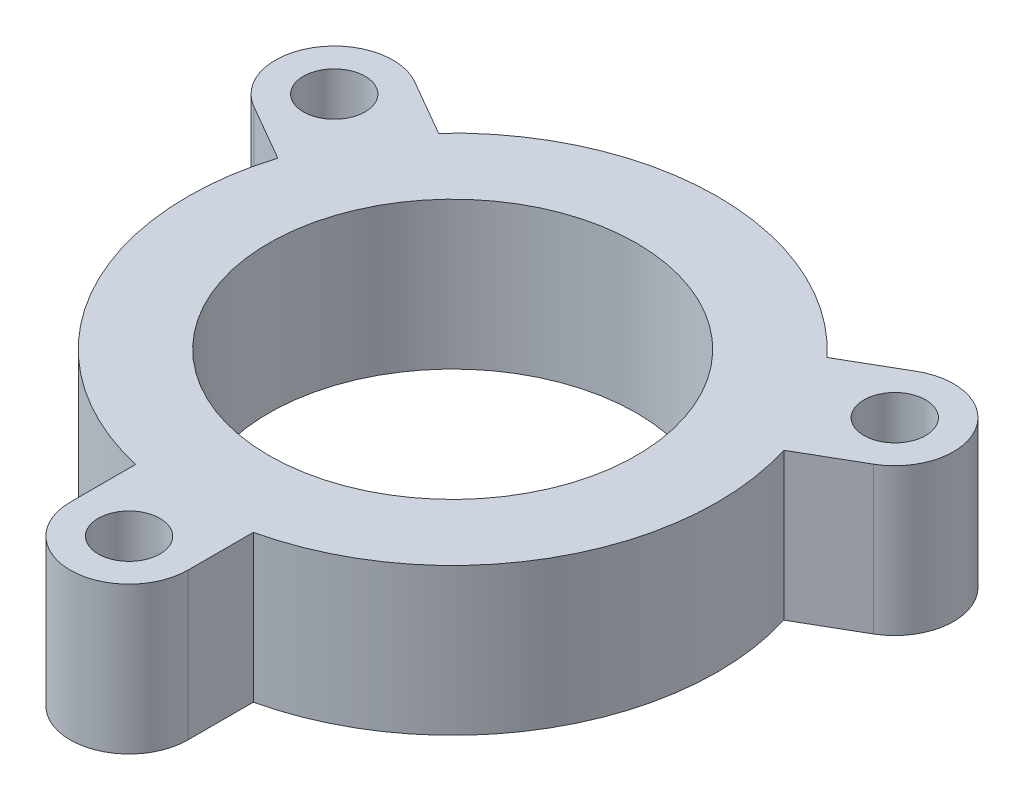
SolidWorks part; units mm, degrees
ref_plane "Front Plane" through (0, 0, 0) normal (0, 0, 1) x (1, 0, 0)
ref_plane "Top Plane" through (0, 0, 0) normal (0, 1, 0) x (1, 0, 0)
ref_plane "Right Plane" through (0, 0, 0) normal (1, 0, 0) x (0, 0, -1)
sketch "Sketch1" plane through (0, 0, 0) normal (0, 1, 0) x (1, 0, 0)
  line L0 (4, -22) -> (4, -17.5499)
  line L1 (-4, -22) -> (-4, -17.5499)
  line L2 (-21.0526, 7.5359) -> (-17.1987, 5.3109)
  line L3 (-17.0526, 14.4641) -> (-13.1987, 12.2391)
  line L4 (17.0526, 14.4641) -> (13.1987, 12.2391)
  line L5 (21.0526, 7.5359) -> (17.1987, 5.3109)
  circle A0 centre (0, 0) radius 18
  circle A1 centre (0, 0) radius 12.5
  circle A2 centre (0, -22) radius 2.1
  circle A3 centre (0, -22) radius 4
  circle A4 centre (-19.0526, 11) radius 4
  circle A5 centre (-19.0526, 11) radius 2.1
  circle A6 centre (19.0526, 11) radius 4
  circle A7 centre (19.0526, 11) radius 2.1
  point P28 (0, 0)
  dimension "D1" = 36
  dimension "D2" = 25
  dimension "D3" = 4.2
  dimension "D4" = 8
  dimension "D5" = 22
  dimension "D6" = 3
extrude "Boss-Extrude1" add sketch "Sketch1" along normal blind 10 contours A0 A1 | A6 A7 | A6 A0 L5 | A6 L4 A0 | A4 A0 L3 | A4 A5 | A4 L2 A0 | A3 A2 | A3 L0 A0 | A3 A0 L1 | A3 | A2 region at (3.0911, 0, 18.7412) region at (0, 0, 25.8869) region at (1.9557, 0, 17.3812) region at (-3.0911, 0, 18.7412) region at (17.7759, 0, -6.6936) region at (-17.7759, 0, -6.6936) region at (18.0466, 0, -7.2456) region at (14.6848, 0, -12.0476) region at (-22.4187, 0, -12.9434) region at (-14.6848, 0, -12.0476)
